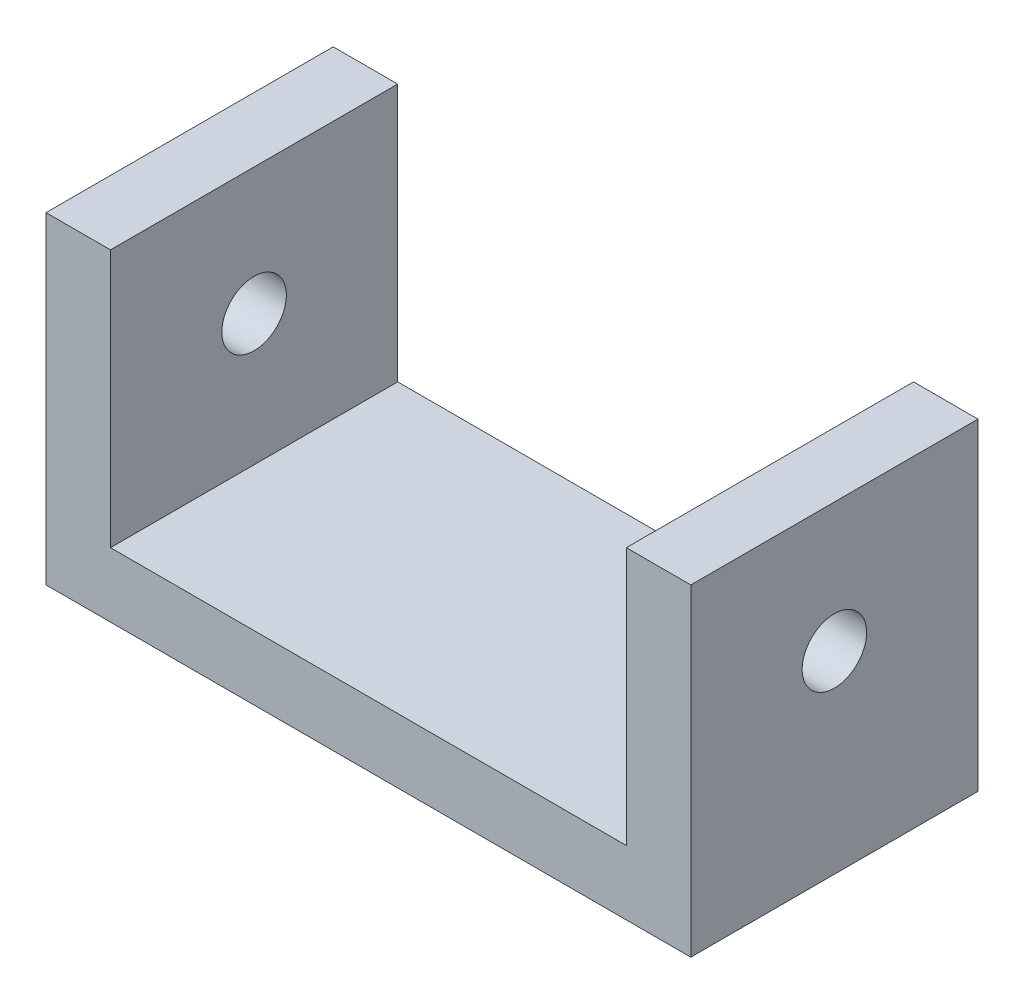
SolidWorks part; units mm, degrees
ref_plane "Front Plane" through (0, 0, 0) normal (0, 0, 1) x (1, 0, 0)
ref_plane "Top Plane" through (0, 0, 0) normal (0, 1, 0) x (1, 0, 0)
ref_plane "Right Plane" through (0, 0, 0) normal (1, 0, 0) x (0, 0, -1)
sketch "Sketch1" plane through (0, 0, 0) normal (0, 1, 0) x (1, 0, 0)
  line L1 (-31.75, 14.1421) -> (31.75, 14.1421)
  line L2 (-31.75, 14.1421) -> (-31.75, -14.1421)
  line L3 (-31.75, -14.1421) -> (31.75, -14.1421)
  line L4 (31.75, 14.1421) -> (31.75, -14.1421)
  line L5 (-31.75, 14.1421) -> (31.75, -14.1421) construction
  line L6 (-31.75, -14.1421) -> (31.75, 14.1421) construction
  point P0 (0, 0)
  dimension "D1" = 63.5
extrude "Boss-Extrude1" add sketch "Sketch1" along normal blind 6.35
sketch "Sketch2" plane through (0, 6.35, 0) normal (0, 1, 0) x (1, 0, 0)
  line L0 (-31.75, -14.1421) -> (31.75, -14.1421) construction
  line L1 (-31.75, 14.1421) -> (-25.4, 14.1421)
  line L2 (-31.75, 14.1421) -> (-31.75, -14.1421)
  line L3 (-31.75, -14.1421) -> (-25.4, -14.1421)
  line L4 (-25.4, 14.1421) -> (-25.4, -14.1421)
  line L6 (31.75, 14.1421) -> (25.4, 14.1421)
  line L7 (31.75, 14.1421) -> (31.75, -14.1421)
  line L8 (31.75, -14.1421) -> (25.4, -14.1421)
  line L9 (25.4, 14.1421) -> (25.4, -14.1421)
  dimension "D1" = 6.35
  dimension "D2" = 6.35
extrude "Boss-Extrude2" add sketch "Sketch2" along normal blind 25.4
sketch "Sketch3" plane through (-31.75, 0, 0) normal (-1, 0, 0) x (0, 0, 1)
  line L0 (-14.1421, 6.7458) -> (14.1421, 31.75) construction
  line L1 (-14.1421, 31.75) -> (-14.1421, 0) construction
  line L2 (-14.1421, 31.75) -> (14.1421, 6.7458) construction
  line L3 (14.1421, 31.75) -> (14.1421, 0) construction
  circle A0 centre (0, 19.2479) radius 3.175
  dimension "D1" = 6.35
extrude "Cut-Extrude1" cut sketch "Sketch3" against normal blind 6.35
sketch "Sketch4" plane through (31.75, 0, 0) normal (1, 0, 0) x (0, 0, -1)
  line L0 (-14.1421, 6.35) -> (14.1421, 31.75) construction
  line L1 (-14.1421, 31.75) -> (14.1421, 6.35) construction
  circle A0 centre (0, 19.05) radius 3.175
  dimension "D1" = 6.35
extrude "Cut-Extrude2" cut sketch "Sketch4" against normal blind 7.62 contours A0
